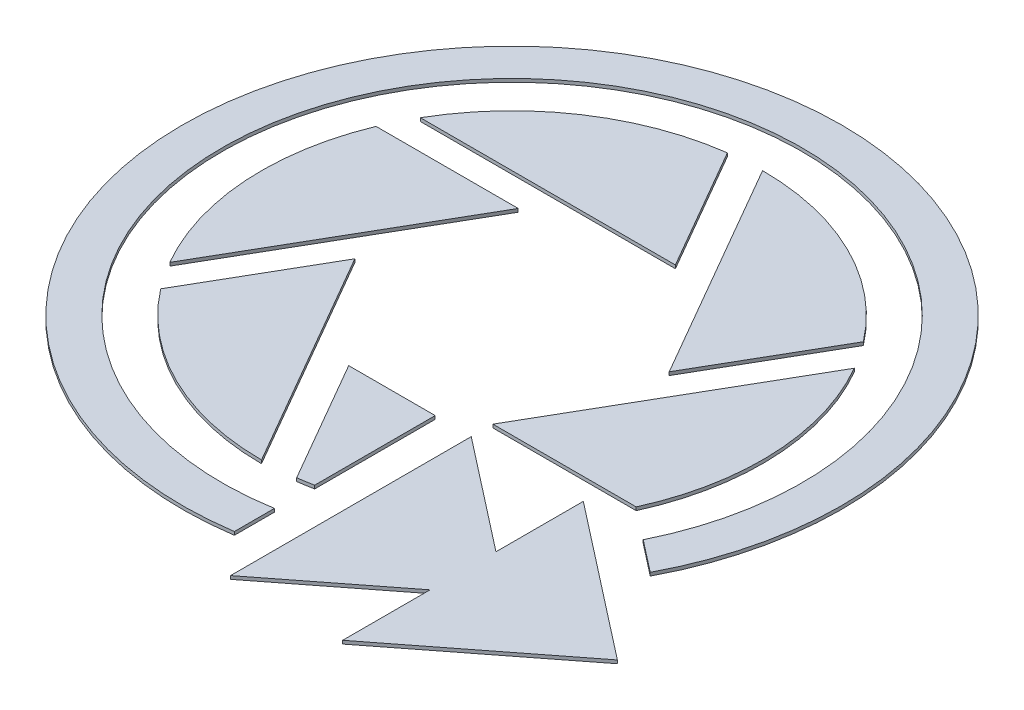
SolidWorks part; units mm, degrees
ref_plane "前视基准面" through (0, 0, 0) normal (0, 0, 1) x (1, 0, 0)
ref_plane "上视基准面" through (0, 0, 0) normal (0, 1, 0) x (1, 0, 0)
ref_plane "右视基准面" through (0, 0, 0) normal (1, 0, 0) x (0, 0, -1)
other "Configuration Table"
sketch "草图1" plane through (0, 0, 0) normal (0, 1, 0) x (1, 0, 0)
  line L0 (-2097.4547, -11.9316) -> (-770.8759, -11.9316) construction
  line L1 (-109.6966, 190) -> (-329.0897, 190)
  line L2 (128.4499, -157.5182) -> (219.3931, 0)
  line L3 (193.4123, 45) -> (109.6966, 190)
  line L4 (57.735, 190) -> (-109.6966, 190)
  line L5 (-135.6773, 145) -> (-219.3931, 0)
  line L6 (-193.4123, -45) -> (-109.6966, -190)
  line L7 (-57.735, -190) -> (73.4499, -190)
  line L8 (-135.6773, 145) -> (-351.2478, 145)
  line L9 (-219.3931, 0) -> (-329.0897, -190)
  line L10 (-193.4123, -45) -> (-301.1976, -231.6895)
  line L11 (-109.6966, -190) -> (0, -380)
  line L12 (-57.735, -190) -> (50.0502, -376.6895)
  line L13 (73.4499, -190) -> (73.4499, -372.8339)
  line L14 (-50.0502, 376.6895) -> (57.735, 190)
  line L15 (109.6966, 190) -> (0, 380)
  line L16 (219.3931, 0) -> (329.0897, 190)
  line L17 (301.1976, 231.6895) -> (193.4123, 45)
  line L18 (128.4499, -157.5182) -> (345.815, -157.5182)
  line L19 (128.4499, -190.3339) -> (128.4499, -555.3339)
  line L20 (128.4499, -555.3339) -> (298.4499, -422.8339)
  line L21 (298.4499, -422.8339) -> (298.4499, -555.3339)
  line L22 (298.4499, -555.3339) -> (532.6009, -372.8339)
  line L26 (128.4499, -372.8339) -> (532.6009, -372.8339) construction
  line L30 (298.4499, -190.3339) -> (532.6009, -372.8339)
  line L31 (298.4499, -322.8339) -> (298.4499, -190.3339)
  line L32 (128.4499, -190.3339) -> (298.4499, -322.8339)
  line L33 (73.4499, -433.8261) -> (73.4499, -494.5757)
  line L34 (394.2838, -195.2953) -> (442.4701, -232.8523)
  circle A3 centre (0, 0) radius 190 construction
  arc A4 (394.2838, -195.2953) -> (73.4499, -433.8261) centre (0, 0) ccw
  arc A5 (442.4701, -232.8523) -> (73.4499, -494.5757) centre (0, 0) ccw
  arc A6 (50.0502, -376.6895) -> (73.4499, -372.8339) centre (0, 0) ccw
  arc A7 (-301.1976, -231.6895) -> (0, -380) centre (0, 0) ccw
  arc A8 (-351.2478, 145) -> (-329.0897, -190) centre (0, 0) ccw
  arc A9 (-50.0502, 376.6895) -> (-329.0897, 190) centre (0, 0) ccw
  arc A10 (301.1976, 231.6895) -> (0, 380) centre (0, 0) ccw
  arc A11 (345.815, -157.5182) -> (329.0897, 190) centre (0, 0) ccw
  point P3 (84.7792, 231.6895)
  point P4 (0, 0)
  point P6 (0, 0)
  point P10 (113.6201, 183.2042)
  point P41 (0, 0)
  point P42 (0, 0)
  point P43 (0, 0)
  point P44 (0, 0)
  point P49 (395.8918, -189.3954)
  point P50 (0, 0)
  dimension "D2" = 500
  dimension "D12" = 380
  dimension "D5" = 45
  dimension "D7" = 219.3931
  dimension "D6" = 45
  dimension "D8" = 45
  dimension "D9" = 45
  dimension "D10" = 45
  dimension "D11" = 51.9615
  dimension "D14" = 55
  dimension "D13" = 365
  dimension "D15" = 170
  dimension "D16" = 100
  dimension "D17" = 55
  dimension "D3" = 60
  dimension "D4" = 60
extrude "凸台-拉伸1" add sketch "草图1" along normal blind 5
equation "\"D6@草图1\"=\"D5@草图1\""
equation "\"D8@草图1\"=\"D5@草图1\""
equation "\"D10@草图1\"=\"D5@草图1\""
equation "\"D14@草图1\"=\"D17@草图1\""
equation "\"D4@草图1\"=\"D3@草图1\""
